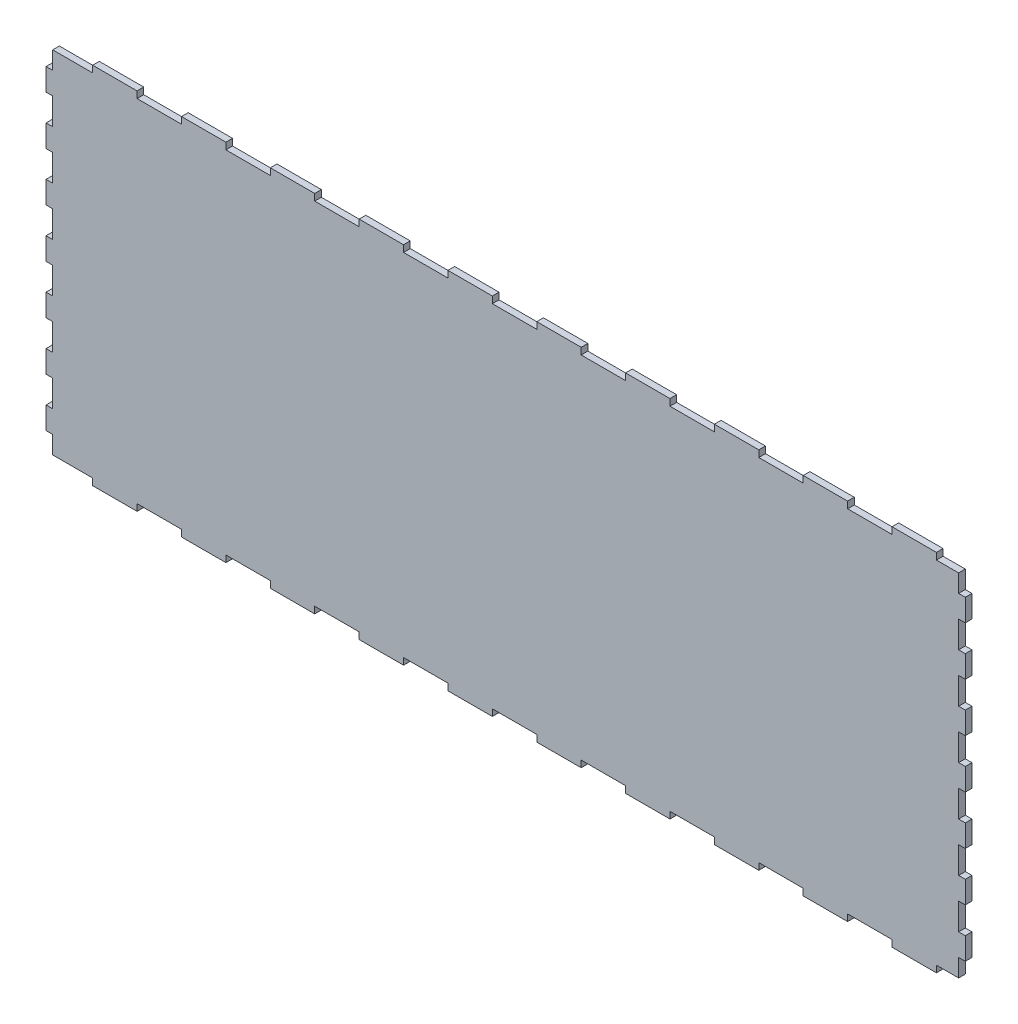
SolidWorks part; units mm, degrees
material "birch 3mm plywood"
ref_plane "Front Plane" through (0, 0, 0) normal (0, 0, 1) x (1, 0, 0)
ref_plane "Top Plane" through (0, 0, 0) normal (0, 1, 0) x (1, 0, 0)
ref_plane "Right Plane" through (0, 0, 0) normal (1, 0, 0) x (0, 0, -1)
sketch "Sketch1" plane through (0, 0, 152) normal (0, 0, 1) x (1, 0, 0)
  line L1 (-207, 82) -> (207, 82)
  line L2 (-207, 82) -> (-207, -82)
  line L3 (-207, -82) -> (207, -82)
  line L4 (207, 82) -> (207, -82)
  line L12 (200, -75) -> (-200, -75) construction
  line L13 (200, 75) -> (200, -75) construction
  line L14 (-200, -75) -> (-200, 75) construction
  line L15 (-200, 75) -> (200, 75) construction
  line L26 (-200, 0) -> (200, 0) construction
  line L31 (-200, 0) -> (200, 0) construction
  point P4 (336.5, -85.9413)
  point P6 (-65.8963, -157.7971)
  point P14 (0, 0)
  point P15 (0, 0)
  point P32 (-47.5, -25.9413)
  point P35 (256.981, -145.9413)
  point P38 (10.8894, 25.9413)
  point P51 (10.8894, -25.9413)
  point P54 (256.981, 145.9413)
  dimension "D1" = 7
  dimension "D2" = 7
  dimension "D3" = 7
  dimension "D4" = 7
  dimension "D5" = 150
  dimension "D6" = 400
extrude "Boss-Extrude1" add sketch "Sketch1" along normal blind 3
sketch "Sketch2" plane through (-207, 0, 0) normal (-1, 0, 0) x (0, 0, 1)
  line L7 (155, -82) -> (152, -82)
  line L8 (152, -82) -> (152, -71)
  line L9 (152, 82) -> (155, 82)
  line L10 (155, 82) -> (155, 71)
  line L11 (152, -61) -> (152, -49)
  line L12 (155, -71) -> (155, -82)
  line L13 (155, -49) -> (155, -61)
  line L14 (152, -39) -> (152, -27)
  line L15 (152, -17) -> (152, -5)
  line L16 (155, -27) -> (155, -39)
  line L17 (155, -5) -> (155, -17)
  line L18 (152, 5) -> (152, 17)
  line L19 (152, 27) -> (152, 39)
  line L20 (155, 17) -> (155, 5)
  line L21 (155, 39) -> (155, 27)
  line L22 (152, 49) -> (152, 61)
  line L23 (152, 71) -> (152, 82)
  line L24 (155, 61) -> (155, 49)
  line L76 (67, 82) -> (57, 82)
  line L77 (57, 82) -> (57, 79)
  line L78 (57, 79) -> (45, 79)
  line L79 (45, 79) -> (45, 82)
  line L80 (45, 82) -> (35, 82)
  line L81 (35, 82) -> (35, 79)
  line L82 (35, 79) -> (23, 79)
  line L83 (23, 79) -> (23, 82)
  line L84 (23, 82) -> (16, 82)
  line L85 (16, 82) -> (16, -82)
  line L86 (16, -82) -> (23, -82)
  line L87 (23, -82) -> (23, -79)
  line L88 (23, -79) -> (35, -79)
  line L89 (35, -79) -> (35, -82)
  line L90 (35, -82) -> (45, -82)
  line L91 (45, -82) -> (45, -79)
  line L92 (45, -79) -> (57, -79)
  line L93 (57, -79) -> (57, -82)
  line L94 (57, -82) -> (67, -82)
  line L95 (67, -82) -> (67, -79)
  line L96 (67, -79) -> (79, -79)
  line L97 (79, -79) -> (79, -82)
  line L98 (79, -82) -> (89, -82)
  line L99 (89, -82) -> (89, -79)
  line L100 (89, -79) -> (101, -79)
  line L101 (101, -79) -> (101, -82)
  line L102 (101, -82) -> (111, -82)
  line L103 (133, -82) -> (133, -79)
  line L104 (133, -79) -> (145, -79)
  line L105 (145, -79) -> (145, -82)
  line L106 (145, -82) -> (155, -82)
  line L107 (155, -82) -> (155, -71)
  line L108 (155, -71) -> (152, -71)
  line L109 (152, -71) -> (152, -61)
  line L110 (152, -61) -> (155, -61)
  line L111 (155, -61) -> (155, -49)
  line L112 (155, -49) -> (152, -49)
  line L113 (152, -49) -> (152, -39)
  line L114 (152, -39) -> (155, -39)
  line L115 (155, -39) -> (155, -27)
  line L116 (155, -27) -> (152, -27)
  line L117 (152, -27) -> (152, -17)
  line L118 (152, -17) -> (155, -17)
  line L119 (155, -17) -> (155, -5)
  line L120 (155, -5) -> (152, -5)
  line L121 (152, -5) -> (152, 5)
  line L122 (152, 5) -> (155, 5)
  line L123 (155, 5) -> (155, 17)
  line L124 (155, 17) -> (152, 17)
  line L125 (152, 17) -> (152, 27)
  line L126 (152, 27) -> (155, 27)
  line L127 (155, 27) -> (155, 39)
  line L128 (155, 39) -> (152, 39)
  line L129 (152, 39) -> (152, 49)
  line L130 (152, 49) -> (155, 49)
  line L131 (155, 49) -> (155, 61)
  line L132 (155, 61) -> (152, 61)
  line L133 (152, 61) -> (152, 71)
  line L134 (152, 71) -> (155, 71)
  line L135 (155, 71) -> (155, 82)
  line L136 (155, 82) -> (145, 82)
  line L137 (145, 82) -> (145, 79)
  line L138 (145, 79) -> (133, 79)
  line L139 (133, 79) -> (133, 82)
  line L140 (133, 82) -> (123, 82)
  line L141 (123, 82) -> (123, 79)
  line L142 (123, 79) -> (111, 79)
  line L143 (111, 79) -> (111, 82)
  line L144 (111, 82) -> (101, 82)
  line L145 (101, 82) -> (101, 79)
  line L146 (101, 79) -> (89, 79)
  line L147 (89, 79) -> (89, 82)
  line L148 (89, 82) -> (79, 82)
  line L149 (79, 82) -> (79, 79)
  line L150 (79, 79) -> (67, 79)
  line L151 (67, 79) -> (67, 82)
  line L184 (155, -71) -> (152, -71)
  line L186 (152, -61) -> (155, -61)
  line L188 (155, -49) -> (152, -49)
  line L190 (152, -39) -> (155, -39)
  line L192 (155, -27) -> (152, -27)
  line L194 (152, -17) -> (155, -17)
  line L196 (155, -5) -> (152, -5)
  line L198 (152, 5) -> (155, 5)
  line L200 (155, 17) -> (152, 17)
  line L202 (152, 27) -> (155, 27)
  line L204 (155, 39) -> (152, 39)
  line L206 (152, 49) -> (155, 49)
  line L208 (155, 61) -> (152, 61)
  line L210 (152, 71) -> (155, 71)
  line L565 (111, -82) -> (111, -79)
  line L567 (111, -79) -> (123, -79)
  line L569 (123, -79) -> (123, -82)
  line L571 (123, -82) -> (133, -82)
  dimension "D1" = 0
extrude "Cut-Extrude1" cut sketch "Sketch2" against normal blind 3
mirror "Mirror1" about plane through (0, 0, 0) normal (1, 0, 0) of "Cut-Extrude1"
sketch "Sketch3" plane through (0, 82, 0) normal (0, 1, 0) x (1, 0, 0)
  line L92 (174, -152) -> (194, -152)
  line L93 (194, -152) -> (194, -155)
  line L94 (194, -155) -> (204, -155)
  line L95 (204, -155) -> (204, -145)
  line L96 (204, -145) -> (207, -145)
  line L97 (207, -145) -> (207, -133)
  line L98 (207, -133) -> (204, -133)
  line L99 (204, -133) -> (204, -123)
  line L100 (204, -123) -> (207, -123)
  line L101 (207, -123) -> (207, -111)
  line L102 (207, -111) -> (204, -111)
  line L103 (204, -111) -> (204, -101)
  line L104 (204, -101) -> (207, -101)
  line L105 (207, -101) -> (207, -89)
  line L106 (207, -89) -> (204, -89)
  line L107 (204, -89) -> (204, -79)
  line L108 (204, -79) -> (207, -79)
  line L109 (207, -79) -> (207, -67)
  line L110 (207, -67) -> (204, -67)
  line L111 (204, -67) -> (204, -57)
  line L112 (204, -57) -> (207, -57)
  line L113 (207, -57) -> (207, -45)
  line L114 (207, -45) -> (204, -45)
  line L115 (204, -45) -> (204, -35)
  line L116 (204, -35) -> (207, -35)
  line L117 (207, -35) -> (207, -23)
  line L118 (207, -23) -> (204, -23)
  line L119 (204, -23) -> (204, -16)
  line L120 (204, -16) -> (-204, -16)
  line L121 (-204, -16) -> (-204, -23)
  line L122 (-204, -23) -> (-207, -23)
  line L123 (-207, -23) -> (-207, -35)
  line L124 (-207, -35) -> (-204, -35)
  line L125 (-204, -35) -> (-204, -45)
  line L126 (-204, -45) -> (-207, -45)
  line L127 (-207, -45) -> (-207, -57)
  line L128 (-207, -57) -> (-204, -57)
  line L129 (-204, -57) -> (-204, -67)
  line L130 (-204, -67) -> (-207, -67)
  line L131 (-207, -67) -> (-207, -79)
  line L132 (-207, -79) -> (-204, -79)
  line L133 (-204, -79) -> (-204, -89)
  line L134 (-204, -89) -> (-207, -89)
  line L135 (-207, -89) -> (-207, -101)
  line L136 (-207, -101) -> (-204, -101)
  line L137 (-204, -101) -> (-204, -111)
  line L138 (-204, -111) -> (-207, -111)
  line L139 (-207, -111) -> (-207, -123)
  line L140 (-207, -123) -> (-204, -123)
  line L141 (-204, -123) -> (-204, -133)
  line L142 (-204, -133) -> (-207, -133)
  line L143 (-207, -133) -> (-207, -145)
  line L144 (-207, -145) -> (-204, -145)
  line L145 (-204, -145) -> (-204, -155)
  line L146 (-204, -155) -> (-186, -155)
  line L147 (-186, -155) -> (-186, -152)
  line L148 (-186, -152) -> (-166, -152)
  line L149 (-166, -152) -> (-166, -155)
  line L150 (-166, -155) -> (-146, -155)
  line L151 (-146, -155) -> (-146, -152)
  line L152 (-146, -152) -> (-126, -152)
  line L153 (-126, -152) -> (-126, -155)
  line L154 (-126, -155) -> (-106, -155)
  line L155 (-106, -155) -> (-106, -152)
  line L156 (-106, -152) -> (-86, -152)
  line L157 (-86, -152) -> (-86, -155)
  line L158 (-86, -155) -> (-66, -155)
  line L159 (-66, -155) -> (-66, -152)
  line L160 (-66, -152) -> (-46, -152)
  line L161 (-46, -152) -> (-46, -155)
  line L162 (-46, -155) -> (-26, -155)
  line L163 (-26, -155) -> (-26, -152)
  line L164 (-26, -152) -> (-6, -152)
  line L165 (-6, -152) -> (-6, -155)
  line L166 (-6, -155) -> (14, -155)
  line L167 (14, -155) -> (14, -152)
  line L168 (14, -152) -> (34, -152)
  line L169 (34, -152) -> (34, -155)
  line L170 (34, -155) -> (54, -155)
  line L171 (54, -155) -> (54, -152)
  line L172 (54, -152) -> (74, -152)
  line L173 (74, -152) -> (74, -155)
  line L174 (74, -155) -> (94, -155)
  line L175 (94, -155) -> (94, -152)
  line L176 (94, -152) -> (114, -152)
  line L177 (114, -152) -> (114, -155)
  line L178 (114, -155) -> (134, -155)
  line L179 (134, -155) -> (134, -152)
  line L180 (134, -152) -> (154, -152)
  line L181 (154, -152) -> (154, -155)
  line L182 (154, -155) -> (174, -155)
  line L183 (174, -155) -> (174, -152)
  line L184 (174, -152) -> (194, -152)
  line L185 (194, -152) -> (194, -155)
  line L186 (194, -155) -> (204, -155)
  line L187 (204, -155) -> (204, -145)
  line L188 (204, -145) -> (207, -145)
  line L189 (207, -145) -> (207, -133)
  line L190 (207, -133) -> (204, -133)
  line L191 (204, -133) -> (204, -123)
  line L192 (204, -123) -> (207, -123)
  line L193 (207, -123) -> (207, -111)
  line L194 (207, -111) -> (204, -111)
  line L195 (204, -111) -> (204, -101)
  line L196 (204, -101) -> (207, -101)
  line L197 (207, -101) -> (207, -89)
  line L198 (207, -89) -> (204, -89)
  line L199 (204, -89) -> (204, -79)
  line L200 (204, -79) -> (207, -79)
  line L201 (207, -79) -> (207, -67)
  line L202 (207, -67) -> (204, -67)
  line L203 (204, -67) -> (204, -57)
  line L204 (204, -57) -> (207, -57)
  line L205 (207, -57) -> (207, -45)
  line L206 (207, -45) -> (204, -45)
  line L207 (204, -45) -> (204, -35)
  line L208 (204, -35) -> (207, -35)
  line L209 (207, -35) -> (207, -23)
  line L210 (207, -23) -> (204, -23)
  line L211 (204, -23) -> (204, -16)
  line L212 (204, -16) -> (-204, -16)
  line L213 (-204, -16) -> (-204, -23)
  line L214 (-204, -23) -> (-207, -23)
  line L215 (-207, -23) -> (-207, -35)
  line L216 (-207, -35) -> (-204, -35)
  line L217 (-204, -35) -> (-204, -45)
  line L218 (-204, -45) -> (-207, -45)
  line L219 (-207, -45) -> (-207, -57)
  line L220 (-207, -57) -> (-204, -57)
  line L221 (-204, -57) -> (-204, -67)
  line L222 (-204, -67) -> (-207, -67)
  line L223 (-207, -67) -> (-207, -79)
  line L224 (-207, -79) -> (-204, -79)
  line L225 (-204, -79) -> (-204, -89)
  line L226 (-204, -89) -> (-207, -89)
  line L227 (-207, -89) -> (-207, -101)
  line L228 (-207, -101) -> (-204, -101)
  line L229 (-204, -101) -> (-204, -111)
  line L230 (-204, -111) -> (-207, -111)
  line L231 (-207, -111) -> (-207, -123)
  line L232 (-207, -123) -> (-204, -123)
  line L233 (-204, -123) -> (-204, -133)
  line L234 (-204, -133) -> (-207, -133)
  line L235 (-207, -133) -> (-207, -145)
  line L236 (-207, -145) -> (-204, -145)
  line L237 (-204, -145) -> (-204, -155)
  line L238 (-204, -155) -> (-186, -155)
  line L239 (-186, -155) -> (-186, -152)
  line L240 (-186, -152) -> (-166, -152)
  line L241 (-166, -152) -> (-166, -155)
  line L242 (-166, -155) -> (-146, -155)
  line L243 (-146, -155) -> (-146, -152)
  line L244 (-146, -152) -> (-126, -152)
  line L245 (-126, -152) -> (-126, -155)
  line L246 (-126, -155) -> (-106, -155)
  line L247 (-106, -155) -> (-106, -152)
  line L248 (-106, -152) -> (-86, -152)
  line L249 (-86, -152) -> (-86, -155)
  line L250 (-86, -155) -> (-66, -155)
  line L251 (-66, -155) -> (-66, -152)
  line L252 (-66, -152) -> (-46, -152)
  line L253 (-46, -152) -> (-46, -155)
  line L254 (-46, -155) -> (-26, -155)
  line L255 (-26, -155) -> (-26, -152)
  line L256 (-26, -152) -> (-6, -152)
  line L257 (-6, -152) -> (-6, -155)
  line L258 (-6, -155) -> (14, -155)
  line L259 (14, -155) -> (14, -152)
  line L260 (14, -152) -> (34, -152)
  line L261 (34, -152) -> (34, -155)
  line L262 (34, -155) -> (54, -155)
  line L263 (54, -155) -> (54, -152)
  line L264 (54, -152) -> (74, -152)
  line L265 (74, -152) -> (74, -155)
  line L266 (74, -155) -> (94, -155)
  line L267 (94, -155) -> (94, -152)
  line L268 (94, -152) -> (114, -152)
  line L269 (114, -152) -> (114, -155)
  line L270 (114, -155) -> (134, -155)
  line L271 (134, -155) -> (134, -152)
  line L272 (134, -152) -> (154, -152)
  line L273 (154, -152) -> (154, -155)
  line L274 (154, -155) -> (174, -155)
  line L275 (174, -155) -> (174, -152)
  dimension "D1" = 0
extrude "Cut-Extrude2" cut sketch "Sketch3" against normal blind 3
mirror "Mirror2" about plane through (0, 0, 0) normal (0, 1, 0) of "Cut-Extrude2"
